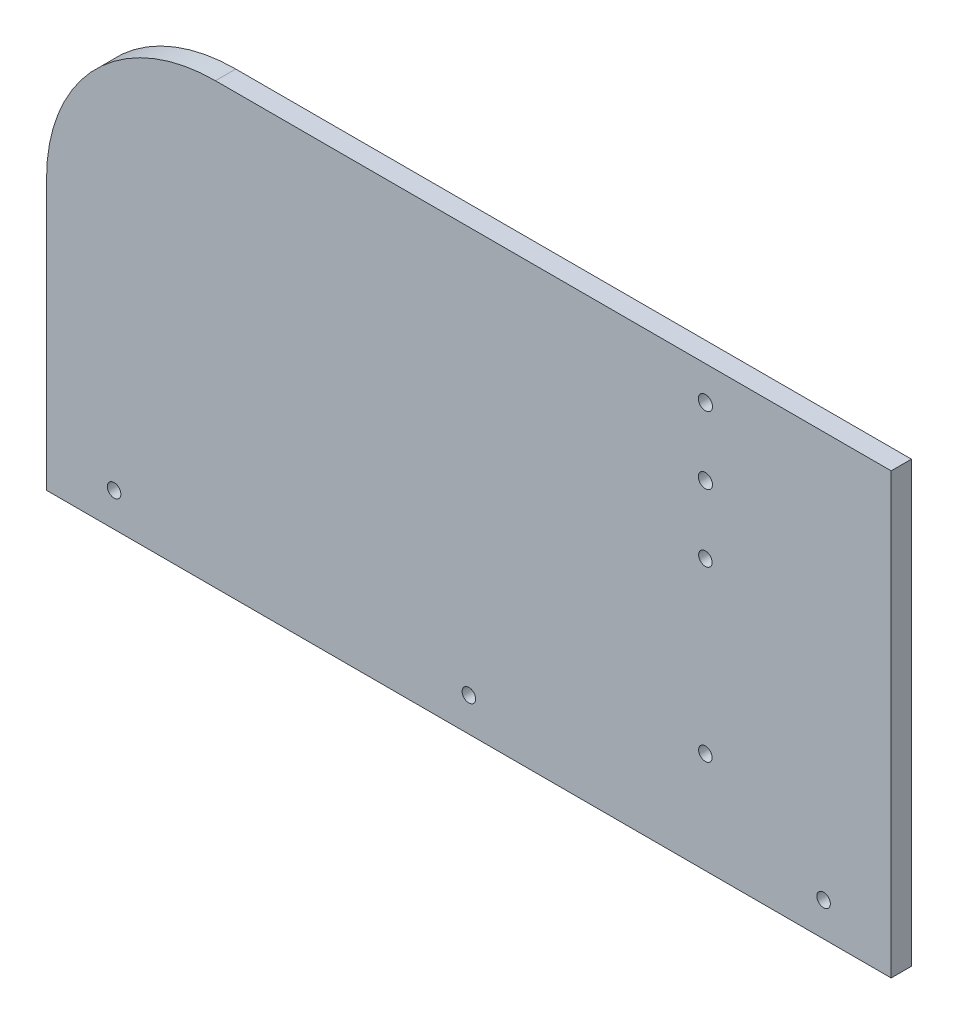
SolidWorks part; units mm, degrees
ref_plane "Plano frontal" through (0, 0, 0) normal (0, 0, 1) x (1, 0, 0)
ref_plane "Plano superior" through (0, 0, 0) normal (0, 1, 0) x (1, 0, 0)
ref_plane "Plano direito" through (0, 0, 0) normal (1, 0, 0) x (0, 0, -1)
sketch "Esboço1" plane through (0, 0, 0) normal (0, 0, 1) x (1, 0, 0)
  line L1 (-125, 65) -> (125, 65)
  line L2 (-125, 65) -> (-125, -65)
  line L3 (-125, -65) -> (125, -65)
  line L4 (125, 65) -> (125, -65)
  line L5 (-125, 65) -> (125, -65) construction
  line L6 (-125, -65) -> (125, 65) construction
  point P0 (0, 0)
  dimension "D1" = 250
  dimension "D2" = 130
extrude "Ressalto-extrusão1" add sketch "Esboço1" along normal blind 6
fillet "Filete1" radius 50 1 edges at (-125, 65, 3)
sketch "Esboço2" plane through (0, 0, 0) normal (0, 0, -1) x (-1, 0, 0)
  line L2 (125, -55) -> (-125, -55)
  line L3 (125, -55) -> (-125, -55) construction
  line L7 (105, 15) -> (105, -65)
  line L8 (105, 15) -> (105, -65) construction
  line L10 (-105, -65) -> (-105, 65)
  line L11 (-105, -65) -> (-105, 65) construction
  circle A0 centre (0, -55) radius 2
  circle A1 centre (105, -55) radius 2
  circle A2 centre (-105, -55) radius 2
  dimension "D4" = 4
  dimension "D1" = 10
  dimension "D2" = 20
  dimension "D3" = 20
extrude "Corte-extrusão1" cut sketch "Esboço2" against normal up to surface (6 mm away) up to face at (-17.0711, 5.0711, 6)
sketch "Esboço3" plane through (0, 0, 0) normal (0, 0, -1) x (-1, 0, 0)
  circle A0 centre (-70, 55) radius 2.1 construction
  circle A1 centre (-70, 35) radius 2.1 construction
  circle A2 centre (-70, 55) radius 2.1
  circle A3 centre (-70, 35) radius 2.1
extrude "Corte-extrusão2" cut sketch "Esboço3" against normal up to surface (6 mm away) up to face at (-103, -55, 6)
sketch "Esboço4" plane through (0, 0, 0) normal (0, 0, -1) x (-1, 0, 0)
  line L0 (-70, 15) -> (-70, -35) construction
  line L1 (-70, -34.55) -> (-70, -55.45) construction
  line L2 (-70, -10) -> (-42.9462, -10) construction
  line L3 (-59, -10) -> (-81, -10) construction
  circle A0 centre (-70, 15) radius 2
  circle A1 centre (-70, -35) radius 2
  dimension "D1" = 4
  dimension "D2" = 50
extrude "Corte-extrusão3" cut sketch "Esboço4" against normal up to surface (6 mm away) up to face at (72.1, 55, 6)
